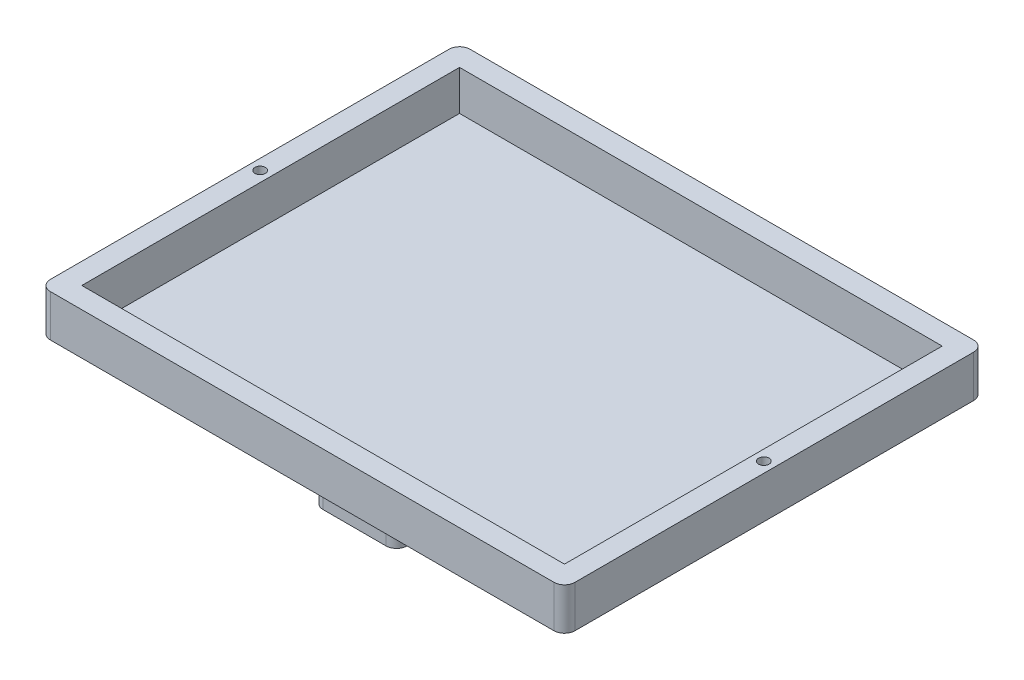
SolidWorks part; units mm, degrees
ref_plane "Front Plane" through (0, 0, 0) normal (0, 0, 1) x (1, 0, 0)
ref_plane "Top Plane" through (0, 0, 0) normal (0, 1, 0) x (1, 0, 0)
ref_plane "Right Plane" through (0, 0, 0) normal (1, 0, 0) x (0, 0, -1)
sketch "Sketch3" plane through (0, 0, 0) normal (0, 0, 1) x (1, 0, 0)
  line L1 (0, 0) -> (70, 0)
  line L2 (0, 0) -> (0, 60)
  line L3 (0, 60) -> (70, 60)
  line L4 (70, 0) -> (70, 60)
  dimension "D1" = 60
  dimension "D2" = 70
extrude "Boss-Extrude1" add sketch "Sketch3" along normal blind 20
sketch "Sketch4" plane through (0, 0, 0) normal (0, 0, 1) x (1, 0, 0)
  line L0 (0, 60) -> (0, 0) construction
  line L1 (0, 60) -> (0, 0)
  line L2 (70, 0) -> (70, 60) construction
  line L3 (70, 60) -> (0, 60) construction
  line L4 (70, 60) -> (70, 0)
  arc A0 (0, 0) -> (0, 60) centre (0, 30) cw
  arc A1 (70, 0) -> (70, 60) centre (70, 30) ccw
extrude "Boss-Extrude2" add sketch "Sketch4" along normal blind 20
sketch "Sketch5" plane through (0, 0, 0) normal (0, 0, 1) x (1, 0, 0)
  line L1 (-30, 30) -> (100, 30) construction
  arc A0 (70, 0) -> (70, 60) centre (70, 30) ccw construction
  arc A1 (0, 60) -> (0, 0) centre (0, 30) ccw construction
  circle A2 centre (20.25, 30) radius 0.75
  point P11 (35, 30)
  dimension "D1" = 14.75
extrude "Cut-Extrude1" cut sketch "Sketch5" along normal through all
sketch "Sketch7" plane through (0, 0, 20) normal (0, 0, 1) x (1, 0, 0)
  line L0 (-30, 30) -> (100, 30) construction
  arc A0 (0, 60) -> (0, 0) centre (0, 30) ccw construction
  arc A1 (70, 0) -> (70, 60) centre (70, 30) ccw construction
  circle A2 centre (49.75, 30) radius 0.75
  point P10 (35, 30)
  dimension "D1" = 14.75
extrude "Cut-Extrude2" cut sketch "Sketch7" against normal through all
ref_axis "Axis2" through (-30, 30, 20) along (1, 0, 0)
pattern_linear "LPattern2" count 3 spacing 2 along (1, 0, 0) of "Cut-Extrude1"
pattern_linear "LPattern3" count 3 spacing 2 along (-1, 0, 0) of "Cut-Extrude2"
sketch "Sketch8" plane through (0, 60, 0) normal (0, 1, 0) x (1, 0, 0)
  line L0 (70, 0) -> (0, 0) construction
  line L1 (-90, 90) -> (160, 90)
  line L2 (-90, 90) -> (-90, -110)
  line L3 (-90, -110) -> (160, -110)
  line L4 (160, 90) -> (160, -110)
  line L5 (70, -20) -> (70, 0) construction
  dimension "D1" = 200
  dimension "D2" = 250
  dimension "D3" = 90
  dimension "D4" = 90
extrude "Boss-Extrude3" add sketch "Sketch8" along normal blind 20
sketch "Sketch9" plane through (0, 80, 0) normal (0, 1, 0) x (1, 0, 0)
  line L8 (-80, 80) -> (-80, -100)
  line L9 (-80, -100) -> (150, -100)
  line L10 (150, -100) -> (150, 80)
  line L11 (150, 80) -> (-80, 80)
  line L12 (-80, 80) -> (-80, -100)
  line L13 (-80, -100) -> (150, -100)
  line L14 (150, -100) -> (150, 80)
  line L15 (150, 80) -> (-80, 80)
  dimension "D1" = 10
extrude "Cut-Extrude3" cut sketch "Sketch9" against normal blind 19
sketch "Sketch10" plane through (0, 60, 0) normal (0, -1, 0) x (1, 0, 0)
  line L0 (160, 110) -> (160, -90) construction
  line L1 (15, 85) -> (55, 85)
  line L2 (15, 85) -> (15, 45)
  line L3 (15, 45) -> (55, 45)
  line L4 (55, 85) -> (55, 45)
  line L5 (-30, 20) -> (100, 20) construction
  dimension "D1" = 40
  dimension "D2" = 40
  dimension "D3" = 105
  dimension "D4" = 25
extrude "Boss-Extrude4" add sketch "Sketch10" along normal blind 30
sketch "Sketch11" plane through (0, 30, 0) normal (0, -1, 0) x (1, 0, 0)
  line L8 (18, 82) -> (18, 48)
  line L9 (18, 48) -> (52, 48)
  line L10 (52, 48) -> (52, 82)
  line L11 (52, 82) -> (18, 82)
  line L12 (18, 82) -> (18, 48)
  line L13 (18, 48) -> (52, 48)
  line L14 (52, 48) -> (52, 82)
  line L15 (52, 82) -> (18, 82)
  dimension "D1" = 3
extrude "Cut-Extrude4" cut sketch "Sketch11" against normal blind 28.5
sketch "Sketch19" plane through (0, 58.5, 0) normal (0, -1, 0) x (1, 0, 0)
  line L0 (18, 82) -> (18, 48) construction
  line L1 (22.555, 77.31) -> (27.555, 77.31)
  line L2 (22.555, 77.31) -> (22.555, 72.31)
  line L3 (22.555, 72.31) -> (27.555, 72.31)
  line L4 (27.555, 77.31) -> (27.555, 72.31)
  line L5 (52, 82) -> (18, 82) construction
  dimension "D1" = 5
  dimension "D2" = 5
  dimension "D3" = 4.555
  dimension "D4" = 4.69
extrude "Boss-Extrude5" add sketch "Sketch19" along normal blind 10
hole_wizard "Ø3.0mm Dowel Hole1" positions "Sketch21" profile "Sketch22" hole size "Ø3.0" standard "ANSI Metric"
sketch "Sketch21" plane through (0, 48.5, 0) normal (0, -1, 0) x (-1, 0, 0)
  line L0 (-27.555, -77.31) -> (-22.555, -77.31) construction
  line L1 (-22.555, -77.31) -> (-22.555, -72.31) construction
  point P0 (-23.755, -76.11)
  dimension "D1" = 1.2
  dimension "D2" = 1.2
sketch "Sketch22" plane through (23.755, 48.5, 76.11) normal (1, 0, 0) x (0, 0, -1)
  line L0 (0, 0) -> (0, 10.4579)
  line L1 (0, 10.4579) -> (0.762, 10)
  line L2 (0.762, 10) -> (0.762, 0)
  line L5 (0.762, 0) -> (0, 0)
  line L10 (0, 10.4579) -> (-0.762, 10) construction
  line L11 (0, -6.35) -> (0, 107.95) construction
  dimension "Hole Dia." = 1.524
  dimension "Hole Depth" = 10
  dimension "Drill Angle" = 118
ref_plane "Plane1" through (35, 0, 0) normal (1, 0, 0) x (0, 0, -1)
mirror "Mirror1" about plane through (35, 0, 0) normal (1, 0, 0) of "Ø3.0mm Dowel Hole1", "Boss-Extrude5"
ref_plane "Plane2" through (0, 0, 65) normal (0, 0, 1) x (1, 0, 0)
mirror "Mirror2" about plane through (0, 0, 65) normal (0, 0, 1) of "Mirror1"
sketch "Sketch23" plane through (0, 58.5, 0) normal (0, -1, 0) x (1, 0, 0)
  line L1 (18, 82) -> (21, 82)
  line L2 (18, 82) -> (18, 79)
  line L3 (18, 79) -> (21, 79)
  line L4 (21, 82) -> (21, 79)
  dimension "D1" = 3
  dimension "D2" = 3
extrude "Boss-Extrude6" add sketch "Sketch23" along normal blind 28.5
mirror "Mirror3" about plane through (0, 0, 65) normal (0, 0, 1) of "Boss-Extrude6"
mirror "Mirror4" about plane through (35, 0, 0) normal (1, 0, 0) of "Mirror3"
hole_wizard "Ø3.0mm Dowel Hole2" positions "Sketch25" profile "Sketch26" hole size "Ø3.0" standard "ANSI Metric"
sketch "Sketch25" plane through (0, 30, 0) normal (0, -1, 0) x (-1, 0, 0)
  line L0 (-55, -85) -> (-15, -85) construction
  line L1 (-15, -85) -> (-15, -45) construction
  point P0 (-18, -82)
  dimension "D1" = 3
  dimension "D2" = 3
sketch "Sketch26" plane through (18, 30, 82) normal (1, 0, 0) x (0, 0, -1)
  line L0 (0, 0) -> (0, 10.9013)
  line L1 (0, 10.9013) -> (1.5, 10)
  line L2 (1.5, 10) -> (1.5, 0)
  line L5 (1.5, 0) -> (0, 0)
  line L10 (0, 10.9013) -> (-1.5, 10) construction
  line L11 (0, -6.35) -> (0, 107.95) construction
  dimension "Hole Dia." = 3
  dimension "Hole Depth" = 10
  dimension "Drill Angle" = 118
mirror "Mirror5" about plane through (0, 0, 65) normal (0, 0, 1) of "Ø3.0mm Dowel Hole2"
mirror "Mirror6" about plane through (35, 0, 0) normal (1, 0, 0) of "Mirror5"
sketch "Sketch27" plane through (55, 0, 0) normal (1, 0, 0) x (0, 0, -1)
  line L0 (-85, 30) -> (-85, 60) construction
  line L1 (-45, 60) -> (-85, 60) construction
  circle A0 centre (-65, 40) radius 3
  dimension "D1" = 20
  dimension "D2" = 20
extrude "Cut-Extrude5" cut sketch "Sketch27" against normal through all
sketch "Sketch28" plane through (0, 80, 0) normal (0, 1, 0) x (1, 0, 0)
  line L0 (-80, 80) -> (-80, -100) construction
  line L1 (-90, -110) -> (160, -110) construction
  circle A0 centre (-85, -10) radius 2.5
  dimension "D1" = 5
  dimension "D2" = 100
extrude "Cut-Extrude6" cut sketch "Sketch28" against normal blind 4
sketch "Sketch29" plane through (0, 76, 0) normal (0, 1, 0) x (1, 0, 0)
  line L0 (-90, 90) -> (-90, -110) construction
  circle A0 centre (-85, -8.3) radius 0.225
  circle A1 centre (-85, -10) radius 2.5 construction
  dimension "D1" = 5
  dimension "D2" = 1.7
extrude "Cut-Extrude7" cut sketch "Sketch29" against normal through all
sketch "Sketch30" plane through (0, 76, 0) normal (0, 1, 0) x (1, 0, 0)
  line L0 (-90, 90) -> (-90, -110) construction
  circle A0 centre (-85, -11.7) radius 0.225
  circle A1 centre (-85, -10) radius 2.5 construction
  dimension "D1" = 1.7
  dimension "D2" = 5
extrude "Cut-Extrude8" cut sketch "Sketch30" against normal through all
ref_plane "Plane3" through (35, 0, 0) normal (-1, 0, 0) x (0, 0, 1)
mirror "Mirror7" about plane through (35, 0, 0) normal (-1, 0, 0) of "Cut-Extrude8", "Cut-Extrude7", "Cut-Extrude6"
fillet "Fillet1" radius 5 4 edges at (-90, 70, -90) (-90, 70, 110) (160, 70, 110) (160, 70, -90)
fillet "Fillet2" radius 5 4 edges at (55, 45, 45) (55, 45, 85) (15, 45, 45) (15, 45, 85)
